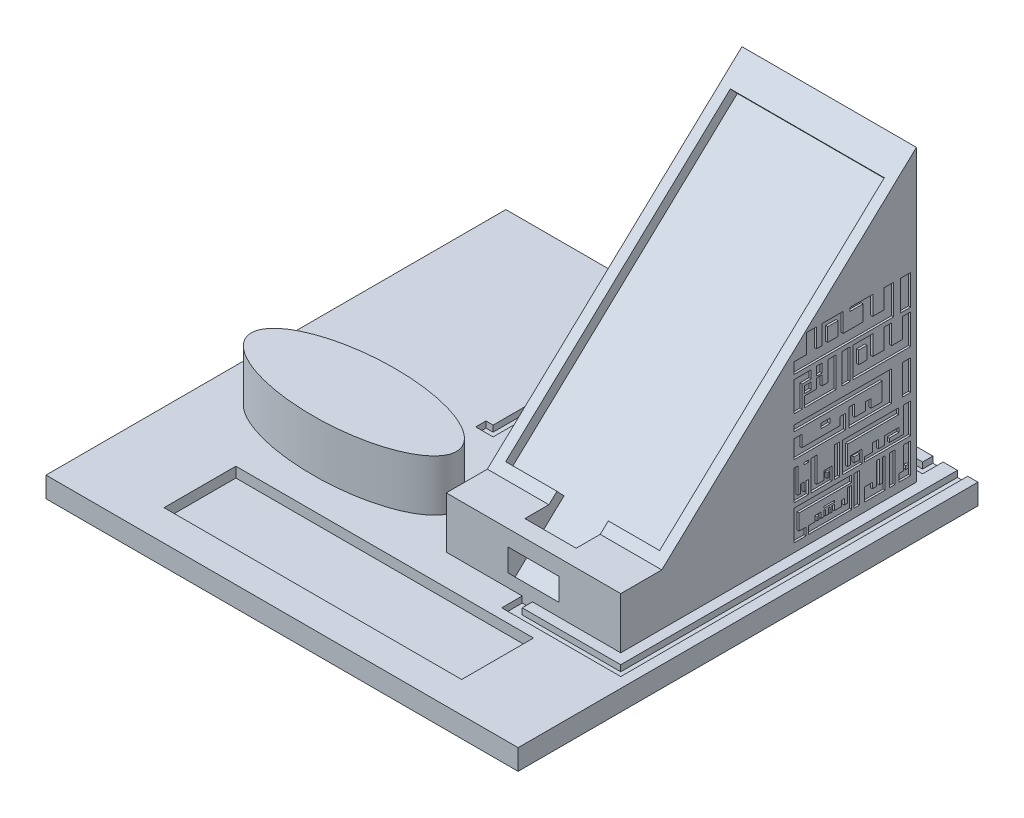
SolidWorks part; units mm, degrees
ref_plane "Front Plane" through (0, 0, 0) normal (0, 0, 1) x (1, 0, 0)
ref_plane "Top Plane" through (0, 0, 0) normal (0, 1, 0) x (1, 0, 0)
ref_plane "Right Plane" through (0, 0, 0) normal (1, 0, 0) x (0, 0, -1)
sketch "Sketch1" plane through (0, 0, 0) normal (0, 1, 0) x (1, 0, 0)
  line L1 (-90.4874, 181.6148) -> (139.5126, 181.6148)
  line L2 (-90.4874, 181.6148) -> (-90.4874, -42.4352)
  line L3 (-90.4874, -42.4352) -> (139.5126, -42.4352)
  line L4 (139.5126, 181.6148) -> (139.5126, -42.4352)
  line L5 (-47.9874, 7.5648) -> (97.0126, 7.5648)
  line L6 (-47.9874, 7.5648) -> (-47.9874, -27.4352)
  line L7 (-47.9874, -27.4352) -> (97.0126, -27.4352)
  line L8 (97.0126, 7.5648) -> (97.0126, -27.4352)
  line L9 (39.5126, 166.6148) -> (124.5126, 166.6148)
  line L10 (39.5126, 166.6148) -> (39.5126, 22.5648)
  line L11 (39.5126, 22.5648) -> (124.5126, 22.5648)
  line L12 (124.5126, 166.6148) -> (124.5126, 22.5648)
  ellipse E0 centre (-25.4874, 42.5648) end of major axis (24.5126, 42.5648) minor radius 20
  dimension "D1" = 15
  dimension "D2" = 15
  dimension "D3" = 145
  dimension "D4" = 35
  dimension "D5" = 85
  dimension "D6" = 144.05
  dimension "D7" = 15
  dimension "D8" = 15
  dimension "D9" = 15
  dimension "D10" = 42.5
  dimension "D11" = 42.5
  dimension "D12" = 15
  dimension "D13" = 15
extrude "Boss-Extrude1" add sketch "Sketch1" against normal blind 10 contours L3 L4 L1 L2
extrude "Boss-Extrude2" add sketch "Sketch1<5>" along normal blind 25 contours E0 region at (-25.4874, 0, -42.5648)
sketch "Sketch1<5>" plane through (0, 0, 0) normal (0, 1, 0) x (1, 0, 0) same geometry as "Sketch1"
extrude "Boss-Extrude3" add sketch "Sketch1<6>" along normal blind 25 contours L12 L9 L10 L11 region at (82.0126, 0, -94.5898)
sketch "Sketch1<6>" plane through (0, 0, 0) normal (0, 1, 0) x (1, 0, 0) same geometry as "Sketch1"
extrude "Cut-Extrude1" cut sketch "Sketch1<8>" against normal blind 5 contours L8 L5 L6 L7 region at (24.5126, 0, 9.9352)
sketch "Sketch1<8>" plane through (0, 0, 0) normal (0, 1, 0) x (1, 0, 0) same geometry as "Sketch1"
sketch "Sketch3" plane through (39.5126, 0, 0) normal (-1, 0, 0) x (0, 0, 1)
  line L0 (-166.6189, 25) -> (-166.6189, 141.2351)
  line L1 (-166.6189, 141.2351) -> (-42.5648, 25)
  line L2 (-166.6148, 25) -> (-22.5648, 25) construction
  line L3 (-42.5648, 25) -> (-166.6189, 25)
  line L4 (-166.6189, 25) -> (-42.5648, 25)
  line M3 (-22.5648, 25) -> (-166.6148, 25)
  dimension "D1" = 170
  dimension "D2" = 20
extrude "Boss-Extrude6" add sketch "Sketch3" against normal up to vertex (85 mm away) contours L1 L0 M3 region at (39.5126, 63.745, -125.2675) up to point (124.5126, 25, -166.6148)
sketch "Sketch5" plane through (0, -7.9248, -7.4253) normal (0, 0.7297, 0.6837) x (1, 0, 0)
  line L0 (39.5126, 218.1542) -> (39.5126, 48.1542) construction
  line L1 (44.5126, 203.5542) -> (119.5126, 203.5542)
  line L2 (44.5126, 203.5542) -> (44.5126, 53.5542)
  line L3 (44.5126, 53.5542) -> (119.5126, 53.5542)
  line L4 (119.5126, 203.5542) -> (119.5126, 53.5542)
  line L5 (124.5126, 218.1542) -> (124.5126, 48.1542) construction
  line L6 (69.5126, 48.1542) -> (94.5126, 48.1542)
  line L7 (124.5126, 48.1542) -> (39.5126, 48.1542) construction
  line L8 (69.5126, 48.1542) -> (69.5126, 15.5805)
  line L9 (69.5126, 15.5805) -> (94.5126, 15.5805)
  line L10 (94.5126, 15.5805) -> (94.5126, 48.1542)
  dimension "D1" = 5
  dimension "D2" = 5
  dimension "D3" = 150
  dimension "D4" = 25
  dimension "D5" = 30
extrude "Cut-Extrude2" cut sketch "Sketch5" against normal blind 5 contours L4 L1 L2 L3 region at (82.0126, 79.9723, -101.2351)
extrude "Cut-Extrude3" cut sketch "Sketch5<3>" along normal blind 8 contours L9 L10 L6 L8
sketch "Sketch5<3>" plane through (0, -7.9248, -7.4253) normal (0, 0.7297, 0.6837) x (1, 0, 0) same geometry as "Sketch5"
sketch "Sketch6" plane through (0, -7.9248, -7.4253) normal (0, 0.7297, 0.6837) x (1, 0, 0)
  line L0 (69.5126, 53.5542) -> (69.5126, 20.7468)
  line L1 (44.5126, 53.5542) -> (119.5126, 53.5542) construction
  line L2 (69.5126, 20.7468) -> (94.5126, 20.7468)
  line L3 (94.5126, 20.7468) -> (94.5126, 53.5542)
  line L4 (94.5126, 53.5542) -> (69.5126, 53.5542)
extrude "Cut-Extrude4" cut sketch "Sketch6" against normal up to surface (5 mm away) up to face at (82.0126, 76.3237, -104.6538)
sketch "Sketch7" plane through (0, 0, 0) normal (0, 1, 0) x (1, 0, 0)
  line L0 (76.5126, 22.5648) -> (76.5126, 12.5648)
  line L1 (39.5126, 22.5648) -> (124.5126, 22.5648) construction
  line L2 (76.5126, 12.5648) -> (134.5126, 12.5648)
  line L3 (134.5126, 12.5648) -> (134.5126, 181.6148)
  line L4 (-90.4874, 181.6148) -> (139.5126, 181.6148) construction
  line L5 (134.5126, 181.6148) -> (129.5126, 181.6148)
  line L6 (129.5126, 181.6148) -> (129.5126, 17.5648)
  line L7 (129.5126, 17.5648) -> (81.5126, 17.5648)
  line L8 (81.5126, 17.5648) -> (81.5126, 22.5648)
  line L9 (39.5126, 22.5648) -> (124.5126, 22.5648) construction
  line L10 (122.5126, 181.6148) -> (122.5126, 171.6148)
  line L11 (122.5126, 171.6148) -> (2.3197, 171.6148)
  line L12 (2.3197, 171.6148) -> (2.3197, 82.5648)
  line L13 (2.3197, 82.5648) -> (-6.1516, 82.5648)
  line L14 (-6.1516, 82.5648) -> (-6.1516, 87.5648)
  line L15 (-6.1516, 87.5648) -> (-2.6803, 87.5648)
  line L16 (-2.6803, 87.5648) -> (-2.6803, 176.6148)
  line L17 (-2.6803, 176.6148) -> (117.5126, 176.6148)
  line L18 (117.5126, 176.6148) -> (117.5126, 181.6148)
  line L19 (117.5126, 181.6148) -> (122.5126, 181.6148)
  line L23 (124.5126, 166.6189) -> (124.5126, 42.5648) construction
  line M5 (139.5126, 181.6148) -> (-90.4874, 181.6148)
  line M7 (124.5126, 22.5648) -> (39.5126, 22.5648)
  dimension "D1" = 5
  dimension "D2" = 5
  dimension "D3" = 5
  dimension "D4" = 5
  dimension "D5" = 5
  dimension "D6" = 5
  dimension "D7" = 5
  dimension "D8" = 5
  dimension "D9" = 7
  dimension "D11" = 5
extrude "Cut-Extrude5" cut sketch "Sketch7" against normal blind 3 contours L7 L8 L0 L2 L3 L6 M7 M5 region at (79.0126, 0, -20.7776)
extrude "Cut-Extrude6" cut sketch "Sketch7<3>" against normal blind 3 contours L16 L17 L18 L19 L10 L11 L12 L13 L14 L15
sketch "Sketch7<3>" plane through (0, 0, 0) normal (0, 1, 0) x (1, 0, 0) same geometry as "Sketch7"
sketch "Sketch14" plane through (0, 0, -166.6189) normal (0, 0, -1) x (-1, 0, 0)
  line L0 (-53.0212, 137.0003) -> (-53.0212, 122.9754)
  line L1 (-53.0212, 122.9754) -> (-103.4158, 122.9754)
  line L2 (-103.4158, 122.9754) -> (-103.4158, 103.7209)
  line L3 (-103.4158, 103.7209) -> (-108.8831, 103.7209)
  line L4 (-108.8831, 103.7209) -> (-108.8831, 136.4733)
  line L5 (-108.8831, 136.4733) -> (-93.432, 136.4733)
  line L6 (-93.432, 136.4733) -> (-93.432, 127.4403)
  line L7 (-93.432, 127.4403) -> (-88.6778, 127.4403)
  line L8 (-88.6778, 127.4403) -> (-88.6778, 136.4733)
  line L9 (-88.6778, 136.4733) -> (-82.9727, 136.4733)
  line L10 (-82.9727, 136.4733) -> (-82.9727, 127.4403)
  line L11 (-82.9727, 127.4403) -> (-78.2185, 127.4403)
  line L12 (-78.2185, 127.4403) -> (-78.2185, 136.4733)
  line L13 (-78.2185, 136.4733) -> (-73.2266, 136.4733)
  line L14 (-73.2266, 136.4733) -> (-73.2266, 127.4403)
  line L15 (-73.2266, 127.4403) -> (-68.2347, 127.4403)
  line L16 (-68.2347, 127.4403) -> (-68.2347, 136.4733)
  line L17 (-68.2347, 136.4733) -> (-63.0051, 136.4733)
  line L18 (-63.0051, 136.4733) -> (-63.0051, 127.9674)
  line L19 (-63.0051, 127.9674) -> (-57.7755, 127.9674)
  line L20 (-57.7755, 127.9674) -> (-57.7755, 137.0003)
  line L21 (-57.7755, 137.0003) -> (-53.0212, 137.0003)
  line L22 (-53.0212, 137.0003) -> (-53.2589, 137.4758)
  line L23 (-103.4158, 132.4838) -> (-103.4158, 127.9674)
  line L24 (-103.4158, 127.9674) -> (-98.1862, 127.9674)
  line L25 (-98.1862, 127.9674) -> (-98.1862, 132.4838)
  line L26 (-98.1862, 132.4838) -> (-103.4158, 132.4838)
  line L27 (-53.0212, 117.0327) -> (-53.0212, 103.7209)
  line L28 (-53.0212, 103.7209) -> (-57.7755, 103.7209)
  line L29 (-57.7755, 103.7209) -> (-57.7755, 117.0327)
  line L30 (-57.7755, 117.0327) -> (-53.0212, 117.0327)
  line L31 (-63.0051, 117.0327) -> (-63.0051, 103.7209)
  line L32 (-63.0051, 103.7209) -> (-98.1862, 103.7209)
  line L33 (-98.1862, 103.7209) -> (-98.1862, 117.0327)
  line L34 (-98.1862, 117.0327) -> (-82.9727, 117.0327)
  line L35 (-82.9727, 117.0327) -> (-82.9727, 108.4751)
  line L36 (-82.9727, 108.4751) -> (-78.2185, 108.4751)
  line L37 (-78.2185, 108.4751) -> (-78.2185, 117.0327)
  line L38 (-78.2185, 117.0327) -> (-73.2266, 117.0327)
  line L39 (-73.2266, 117.0327) -> (-73.2266, 108.4751)
  line L40 (-73.2266, 108.4751) -> (-68.2347, 108.4751)
  line L41 (-68.2347, 108.4751) -> (-68.2347, 117.0327)
  line L42 (-68.2347, 117.0327) -> (-63.0051, 117.0327)
  line L43 (-94.3951, 113.3482) -> (-89.6409, 113.3482)
  line L44 (-89.6409, 113.3482) -> (-89.6409, 108.4751)
  line L45 (-89.6409, 108.4751) -> (-94.3951, 108.4751)
  line L46 (-94.3951, 108.4751) -> (-94.3951, 113.3482)
  line L47 (-53.9844, 98.4913) -> (-53.9844, 93.2617)
  line L48 (-53.9844, 93.2617) -> (-109.8462, 93.2617)
  line L49 (-109.8462, 93.2617) -> (-109.8462, 98.4913)
  line L50 (-109.8462, 98.4913) -> (-53.9844, 98.4913)
  line L51 (-53.9844, 87.5056) -> (-58.7386, 87.5056)
  line L52 (-58.7386, 87.5056) -> (-58.7386, 58.7937)
  line L53 (-58.7386, 58.7937) -> (-63.9682, 58.7937)
  line L54 (-63.9682, 58.7937) -> (-63.9682, 68.5399)
  line L55 (-63.9682, 68.5399) -> (-69.1978, 68.5399)
  line L56 (-69.1978, 68.5399) -> (-69.1978, 58.7937)
  line L57 (-69.1978, 58.7937) -> (-89.6409, 58.7937)
  line L58 (-89.6409, 58.7937) -> (-89.6409, 54.2773)
  line L59 (-89.6409, 54.2773) -> (-53.9844, 54.2773)
  line L60 (-53.9844, 54.2773) -> (-53.9844, 87.5056)
  line L61 (-109.8462, 88.0321) -> (-109.8462, 84.2287)
  line L62 (-109.8462, 84.2287) -> (-69.1978, 84.2287)
  line L63 (-69.1978, 84.2287) -> (-69.1978, 78.5237)
  line L64 (-69.1978, 78.5237) -> (-99.1493, 78.5237)
  line L65 (-99.1493, 78.5237) -> (-99.1493, 58.7937)
  line L66 (-99.1493, 58.7937) -> (-104.3789, 58.7937)
  line L67 (-104.3789, 58.7937) -> (-104.3789, 78.5237)
  line L68 (-104.3789, 78.5237) -> (-109.8462, 78.5237)
  line L69 (-109.8462, 78.5237) -> (-109.8462, 54.2773)
  line L70 (-109.8462, 54.2773) -> (-94.3951, 54.2773)
  line L71 (-94.3951, 54.2773) -> (-94.3951, 73.4129)
  line L72 (-94.3951, 73.4129) -> (-89.522, 73.4129)
  line L73 (-89.522, 73.4129) -> (-89.522, 63.8451)
  line L74 (-89.522, 63.8451) -> (-74.1897, 63.8451)
  line L75 (-74.1897, 63.8451) -> (-74.1897, 73.4129)
  line L76 (-74.1897, 73.4129) -> (-63.9682, 73.4129)
  line L77 (-63.9682, 73.4129) -> (-63.9682, 88.0321)
  line L78 (-63.9682, 88.0321) -> (-109.8462, 88.0321)
  line L79 (-84.1735, 73.4129) -> (-79.4193, 73.4129)
  line L80 (-79.4193, 73.4129) -> (-79.4193, 68.629)
  line L81 (-79.4193, 68.629) -> (-84.1735, 68.629)
  line L82 (-84.1735, 68.629) -> (-84.1735, 73.4129)
  line L83 (-53.9844, 48.2835) -> (-109.8462, 48.2835)
  line L84 (-109.8462, 48.2835) -> (-109.8462, 43.5293)
  line L85 (-109.8462, 43.5293) -> (-53.9844, 43.5293)
  line L86 (-53.9844, 43.5293) -> (-53.9844, 48.2835)
  line L87 (-58.7386, 38.062) -> (-58.7386, 9.2991)
  line L88 (-58.7386, 9.2991) -> (-63.9682, 9.2991)
  line L89 (-63.9682, 9.2991) -> (-63.9682, 19.0452)
  line L90 (-63.9682, 19.0452) -> (-69.1978, 19.0452)
  line L91 (-69.1978, 19.0452) -> (-69.1978, 9.2991)
  line L92 (-69.1978, 9.2991) -> (-109.8462, 9.2991)
  line L93 (-109.8462, 9.2991) -> (-109.8462, 4.7826)
  line L94 (-109.8462, 4.7826) -> (-53.9844, 4.7826)
  line L95 (-53.9844, 4.7826) -> (-53.9844, 38.062)
  line L96 (-53.9844, 38.062) -> (-58.7386, 38.062)
  line L97 (-79.4193, 38.062) -> (-63.9682, 38.062)
  line L98 (-63.9682, 38.062) -> (-63.9682, 23.6805)
  line L99 (-63.9682, 23.6805) -> (-89.522, 23.6805)
  line L100 (-89.522, 23.6805) -> (-89.522, 33.3078)
  line L101 (-89.522, 33.3078) -> (-94.3951, 33.3078)
  line L102 (-94.3951, 33.3078) -> (-94.3951, 23.6805)
  line L103 (-94.3951, 23.6805) -> (-104.3789, 23.6805)
  line L104 (-104.3789, 23.6805) -> (-104.3789, 19.0452)
  line L105 (-104.3789, 19.0452) -> (-76.7451, 19.0452)
  line L106 (-76.7451, 19.0452) -> (-76.7451, 14.1721)
  line L107 (-76.7451, 14.1721) -> (-109.8462, 14.1721)
  line L108 (-109.8462, 14.1721) -> (-109.8462, 38.062)
  line L109 (-109.8462, 38.062) -> (-84.1735, 38.062)
  line L110 (-84.1735, 38.062) -> (-84.1735, 28.4941)
  line L111 (-84.1735, 28.4941) -> (-69.1978, 28.4941)
  line L112 (-69.1978, 28.4941) -> (-69.1978, 33.278)
  line L113 (-69.1978, 33.278) -> (-79.4193, 33.278)
  line L114 (-79.4193, 33.278) -> (-79.4193, 38.062)
  line L115 (-104.3789, 33.8342) -> (-99.387, 33.8342)
  line L116 (-99.387, 33.8342) -> (-99.387, 28.3669)
  line L117 (-99.387, 28.3669) -> (-104.3789, 28.3669)
  line L118 (-104.3789, 28.3669) -> (-104.3789, 33.8342)
  point P121 (0, 0)
  dimension "D5" = 55.8619
  dimension "D8" = 131.6907
extrude "Cut-Extrude7" cut sketch "Sketch14" against normal blind 3 contours L0 L1 L2 L3 L4 L5 L6 L7 L8 L9 L10 L11 L12 L13 L14 L15 L16 L17 L18 L19 L20 L21 | L32 L33 L34 L35 L36 L37 L38 L39 L40 L41 L42 L31 | L27 L28 L29 L30 | L48 L49 L50 L47 | L52 L53 L54 L55 L56 L57 L58 L59 L60 L51 | L77 L78 L61 L62 L63 L64 L65 L66 L67 L68 L69 L70 L71 L72 L73 L74 L75 L76 | L83 L84 L85 L86 | L95 L96 L87 L88 L89 L90 L91 L92 L93 L94 | L98 L99 L100 L101 L102 L103 L104 L105 L106 L107 L108 L109 L110 L111 L112 L113 L114 L97 | L82 L79 L80 L81 | L118 L115 L116 L117 | L25 L26 L23 L24 | L44 L45 L46 L43
sketch "Sketch17" plane through (124.5126, 0, 0) normal (1, 0, 0) x (0, 0, -1)
  line L0 (163.7509, 89.8755) -> (163.7509, 75.2504)
  line L1 (163.7509, 35.6887) -> (163.7509, 21.0637)
  line L2 (163.7509, 35.6887) -> (160.3883, 35.6887)
  line L3 (160.3883, 23.3103) -> (153.4097, 23.3103)
  line L4 (160.3883, 35.6887) -> (160.3883, 23.3103)
  line L5 (163.7509, 75.2504) -> (158.966, 75.2504)
  line L6 (158.966, 75.2504) -> (158.966, 89.8755)
  line L7 (158.966, 89.8755) -> (163.7509, 89.8755)
  line L8 (155.4865, 89.8755) -> (155.4865, 75.2504)
  line L9 (155.4865, 75.2504) -> (155.4865, 89.8755)
  line L10 (150.7016, 89.8755) -> (150.7016, 80.5669)
  line L11 (150.7016, 80.5669) -> (145.3542, 80.5669)
  line L12 (145.3542, 80.5669) -> (145.3542, 89.8755)
  line L13 (145.3542, 89.8755) -> (134.3146, 89.8755)
  line L14 (134.3146, 89.8755) -> (134.3146, 88.2079)
  line L15 (134.3146, 88.2079) -> (140.6177, 88.2079)
  line L16 (140.6177, 88.2079) -> (140.6177, 80.5669)
  line L17 (140.6177, 80.5669) -> (130.8955, 80.5669)
  line L18 (130.8955, 80.5669) -> (130.8955, 89.8755)
  line L19 (130.8955, 89.8755) -> (120.7313, 89.8755)
  line L20 (120.7313, 89.8755) -> (120.7313, 80.5669)
  line L21 (120.7313, 80.5669) -> (117.9693, 80.5669)
  line L22 (117.9693, 80.5669) -> (117.9693, 89.8755)
  line L23 (117.9693, 89.8755) -> (113.1844, 89.8755)
  line L24 (113.1844, 89.8755) -> (113.1844, 80.5669)
  line L25 (113.1844, 80.5669) -> (107.0317, 80.5669)
  line L26 (107.0317, 80.5669) -> (107.0317, 75.2504)
  line L27 (107.0317, 75.2504) -> (155.4865, 75.2504)
  line L28 (136.3964, 27.1688) -> (134.5995, 27.1688)
  line L29 (123.3828, 87.1836) -> (123.3828, 80.5669)
  line L30 (123.3828, 80.5669) -> (128.4393, 80.5669)
  line L31 (128.4393, 80.5669) -> (128.4393, 87.1836)
  line L32 (128.4393, 87.1836) -> (123.3828, 87.1836)
  line L33 (134.5995, 27.1688) -> (134.5995, 23.3103)
  line L34 (150.7016, 89.8755) -> (155.4865, 89.8755)
  line L35 (163.7509, 73.2506) -> (163.7509, 58.6255)
  line L36 (163.7509, 58.6255) -> (159.8999, 58.6255)
  line L37 (159.8999, 73.2506) -> (159.8999, 63.5956)
  line L38 (159.8999, 63.5956) -> (154.5525, 63.5956)
  line L39 (154.5525, 63.5956) -> (154.5525, 73.2506)
  line L40 (154.5525, 73.2506) -> (150.7016, 73.2506)
  line L41 (150.7016, 73.2506) -> (150.7016, 63.5956)
  line L42 (150.7016, 63.5956) -> (145.3542, 63.5956)
  line L43 (145.3542, 63.5956) -> (145.3542, 73.2506)
  line L44 (145.3542, 73.2506) -> (135.7517, 73.2506)
  line L45 (135.7517, 73.2506) -> (135.7517, 58.6255)
  line L46 (135.7517, 58.6255) -> (159.8999, 58.6255)
  line L47 (159.8999, 73.2506) -> (163.7509, 73.2506)
  line L48 (142.5132, 69.8272) -> (138.4798, 69.8272)
  line L49 (138.4798, 69.8272) -> (138.4798, 63.5956)
  line L50 (138.4798, 63.5956) -> (142.5132, 63.5956)
  line L51 (142.5132, 63.5956) -> (142.5132, 69.8272)
  line L52 (133.1522, 14.461) -> (135.1033, 14.461)
  line L53 (134.3146, 73.2506) -> (134.3146, 58.6255)
  line L54 (134.3146, 58.6255) -> (130.4637, 58.6255)
  line L55 (130.4637, 58.6255) -> (130.4637, 73.2506)
  line L56 (130.4637, 73.2506) -> (134.3146, 73.2506)
  line L57 (127.4316, 73.2506) -> (127.4316, 58.6255)
  line L58 (112.0891, 58.6255) -> (127.4316, 58.6255)
  line L59 (151.0136, 27.3684) -> (158.0651, 27.3684)
  line L60 (120.6682, 63.5956) -> (120.6682, 68.2595)
  line L61 (120.6682, 68.2595) -> (117.9506, 68.2595)
  line L62 (117.9506, 68.2595) -> (117.9506, 63.5956)
  line L63 (117.9506, 63.5956) -> (112.0891, 63.5956)
  line L64 (112.0891, 63.5956) -> (112.0891, 58.6255)
  line L65 (158.0651, 25.173) -> (158.0651, 27.3684)
  line L66 (127.4316, 73.2506) -> (123.5807, 73.2506)
  line L67 (123.5807, 73.2506) -> (123.5807, 63.5956)
  line L68 (123.5807, 63.5956) -> (120.6682, 63.5956)
  line L69 (115.3303, 69.2518) -> (115.3303, 73.0449)
  line L70 (115.3303, 73.0449) -> (107.0596, 73.0449)
  line L71 (107.0596, 73.0449) -> (107.0596, 58.6255)
  line L72 (107.0596, 58.6255) -> (110.8904, 58.6255)
  line L73 (110.8904, 58.6255) -> (110.8904, 69.2518)
  line L74 (110.8904, 69.2518) -> (115.3303, 69.2518)
  line L75 (112.0891, 67.9131) -> (112.0891, 64.6631)
  line L76 (112.0891, 64.6631) -> (115.3303, 64.6631)
  line L77 (115.3303, 64.6631) -> (115.3303, 67.9131)
  line L78 (115.3303, 67.9131) -> (112.0891, 67.9131)
  line L79 (117.9506, 69.0586) -> (120.6682, 69.0586)
  line L80 (120.6682, 69.0586) -> (120.6682, 73.2506)
  line L81 (120.6682, 73.2506) -> (117.9506, 73.2506)
  line L82 (117.9506, 73.2506) -> (117.9506, 69.0586)
  line L83 (159.8999, 53.8899) -> (163.7509, 53.8899)
  line L84 (163.7509, 53.8899) -> (163.7509, 39.2648)
  line L85 (163.7509, 39.2648) -> (159.8999, 39.2648)
  line L86 (159.8999, 39.2648) -> (159.8999, 53.8899)
  line L87 (107.0596, 53.8899) -> (154.5525, 53.8899)
  line L88 (154.5525, 53.8899) -> (154.5525, 39.2648)
  line L89 (154.5525, 39.2648) -> (133.768, 39.2648)
  line L90 (133.768, 39.2648) -> (133.768, 48.0938)
  line L91 (133.768, 48.0938) -> (136.4856, 48.0938)
  line L92 (136.4856, 48.0938) -> (136.4856, 42.4185)
  line L93 (136.4856, 42.4185) -> (141.833, 42.4185)
  line L94 (141.833, 42.4185) -> (141.833, 46.3236)
  line L95 (141.833, 46.3236) -> (144.5507, 46.3236)
  line L96 (144.5507, 46.3236) -> (144.5507, 42.2117)
  line L97 (144.5507, 42.2117) -> (149.8981, 42.2117)
  line L98 (149.8981, 42.2117) -> (149.8981, 51.0477)
  line L99 (149.8981, 51.0477) -> (107.0596, 51.0477)
  line L100 (107.0596, 51.0477) -> (107.0596, 53.8899)
  line L101 (129.3931, 46.3236) -> (132.1108, 46.3236)
  line L102 (132.1108, 46.3236) -> (132.1108, 39.2648)
  line L103 (132.1108, 39.2648) -> (107.0596, 39.2648)
  line L104 (107.0596, 39.2648) -> (107.0596, 48.0938)
  line L105 (107.0596, 48.0938) -> (110.8171, 48.0938)
  line L106 (110.8171, 48.0938) -> (110.8171, 42.4185)
  line L107 (110.8171, 42.4185) -> (129.3931, 42.4185)
  line L108 (129.3931, 42.4185) -> (129.3931, 46.3236)
  line L109 (124.4099, 48.0938) -> (120.1218, 48.0938)
  line L110 (120.1218, 48.0938) -> (120.1218, 45.7827)
  line L111 (120.1218, 45.7827) -> (124.4099, 45.7827)
  line L112 (124.4099, 45.7827) -> (124.4099, 48.0938)
  line L113 (145.1752, 27.3019) -> (148.0644, 27.3019)
  line L114 (151.0136, 27.3684) -> (151.0136, 23.3103)
  line L115 (151.0136, 23.3103) -> (148.0644, 23.3103)
  line L116 (148.0644, 23.3103) -> (148.0644, 27.3019)
  line L117 (135.1033, 14.461) -> (135.1033, 10.6261)
  line L118 (145.1752, 27.3019) -> (145.1752, 23.3103)
  line L119 (145.1752, 23.3103) -> (141.3414, 23.3103)
  line L120 (141.3414, 23.3103) -> (141.3414, 21.0637)
  line L121 (141.3414, 21.0637) -> (163.7509, 21.0637)
  line L122 (140.2127, 27.1688) -> (140.2127, 21.0637)
  line L123 (140.2127, 21.0637) -> (130.4871, 21.0637)
  line L124 (134.5995, 23.3103) -> (133.1557, 23.3103)
  line L125 (157.9089, 35.6887) -> (130.4871, 35.6887)
  line L126 (130.4871, 35.6887) -> (130.4871, 21.0637)
  line L127 (121.503, 27.3684) -> (125.537, 27.3684)
  line L128 (157.9089, 35.6887) -> (157.9089, 32.8236)
  line L129 (136.3964, 27.1688) -> (140.2127, 27.1688)
  line L130 (136.2965, 25.8383) -> (138.9079, 25.8383)
  line L131 (138.9079, 25.8383) -> (138.9079, 23.3103)
  line L132 (138.9079, 23.3103) -> (136.2965, 23.3103)
  line L133 (123.0111, 23.3103) -> (123.0111, 25.6387)
  line L134 (136.2965, 25.8383) -> (136.2965, 23.3103)
  line L135 (157.9089, 32.8236) -> (133.1557, 32.8236)
  line L136 (133.1557, 32.8236) -> (133.1557, 23.3103)
  line L137 (129.2293, 35.6887) -> (129.2293, 21.0637)
  line L138 (129.2293, 21.0637) -> (126.6211, 21.0637)
  line L139 (126.6211, 21.0637) -> (126.6211, 35.6887)
  line L140 (126.6211, 35.6887) -> (129.2293, 35.6887)
  line L141 (123.0111, 25.6387) -> (124.0986, 25.6387)
  line L142 (133.1522, 14.461) -> (133.1522, 10.6261)
  line L143 (121.503, 23.3103) -> (121.503, 27.3684)
  line L145 (121.503, 23.3103) -> (118.1167, 23.3103)
  line L146 (118.1167, 23.3103) -> (118.1167, 35.6887)
  line L147 (118.1167, 35.6887) -> (115.3464, 35.6887)
  line L148 (115.3464, 35.6887) -> (115.3464, 21.0637)
  line L149 (115.3464, 21.0637) -> (125.537, 21.0637)
  line L151 (124.0986, 25.6387) -> (124.0986, 23.3103)
  line L153 (153.4097, 25.173) -> (158.0651, 25.173)
  line L154 (124.0986, 23.3103) -> (123.0111, 23.3103)
  line L155 (125.537, 21.1814) -> (125.537, 27.3684)
  line L156 (125.537, 21.1814) -> (125.537, 21.0637)
  line L157 (113.9228, 27.4349) -> (113.9228, 21.0637)
  line L158 (113.9228, 21.0637) -> (107.0596, 21.0637)
  line L159 (107.0596, 21.0637) -> (107.0596, 35.6887)
  line L160 (107.0596, 35.6887) -> (108.87, 35.6887)
  line L161 (108.87, 35.6887) -> (108.87, 23.3103)
  line L162 (108.87, 23.3103) -> (110.1332, 23.3103)
  line L163 (110.1332, 23.3103) -> (110.1332, 27.4349)
  line L164 (110.1332, 27.4349) -> (111.8174, 27.4349)
  line L165 (111.8174, 27.4349) -> (111.8174, 23.3103)
  line L166 (111.8174, 23.3103) -> (112.8701, 23.3103)
  line L167 (112.8701, 23.3103) -> (112.8701, 27.4349)
  line L168 (112.8701, 27.4349) -> (113.9228, 27.4349)
  line L169 (111.8174, 35.6887) -> (113.9228, 35.6887)
  line L170 (113.9228, 35.6887) -> (113.9228, 34.6596)
  line L171 (113.9228, 34.6596) -> (111.8174, 34.6596)
  line L172 (111.8174, 34.6596) -> (111.8174, 35.6887)
  line L173 (109.5016, 35.6887) -> (110.5967, 35.6887)
  line L174 (110.5967, 35.6887) -> (110.5967, 34.6289)
  line L175 (110.5967, 34.6289) -> (109.5016, 34.6289)
  line L176 (109.5016, 34.6289) -> (109.5016, 35.6887)
  line L177 (160.3848, 18.83) -> (163.7475, 18.83)
  line L178 (163.7475, 18.83) -> (163.7475, 4.2049)
  line L179 (163.7475, 4.2049) -> (158.2289, 4.2049)
  line L180 (158.2289, 4.2049) -> (158.2289, 7.9105)
  line L181 (160.3848, 18.83) -> (160.3848, 7.9105)
  line L182 (160.3848, 7.9105) -> (158.2289, 7.9105)
  line L183 (161.4025, 9.5409) -> (161.4025, 7.9105)
  line L184 (161.4025, 7.9105) -> (162.8186, 7.9105)
  line L185 (162.8186, 7.9105) -> (162.8186, 9.5409)
  line L186 (162.8186, 9.5409) -> (161.4025, 9.5409)
  line L187 (156.0847, 18.83) -> (156.0847, 4.2049)
  line L188 (156.0847, 4.2049) -> (153.4097, 4.2049)
  line L189 (153.4097, 4.2049) -> (153.4097, 18.83)
  line L190 (153.4097, 18.83) -> (156.0847, 18.83)
  line L191 (151.3991, 18.83) -> (151.3991, 4.2049)
  line L192 (151.3991, 4.2049) -> (141.338, 4.2049)
  line L193 (141.338, 4.2049) -> (141.338, 10.6261)
  line L194 (141.338, 10.6261) -> (145.1718, 10.6261)
  line L195 (145.1718, 10.6261) -> (145.1718, 7.9105)
  line L196 (145.1718, 7.9105) -> (147.1598, 7.9105)
  line L197 (147.1598, 7.9105) -> (147.1598, 18.83)
  line L198 (147.1598, 18.83) -> (148.515, 18.83)
  line L199 (148.515, 18.83) -> (148.515, 7.9105)
  line L200 (148.515, 7.9105) -> (150.0046, 7.9105)
  line L201 (150.0046, 7.9105) -> (150.0046, 18.83)
  line L202 (150.0046, 18.83) -> (151.3991, 18.83)
  line L203 (142.6973, 9.5409) -> (143.9022, 9.5409)
  line L204 (143.9022, 9.5409) -> (143.9022, 7.9105)
  line L205 (143.9022, 7.9105) -> (142.6973, 7.9105)
  line L206 (142.6973, 7.9105) -> (142.6973, 9.5409)
  line L207 (138.9079, 18.83) -> (138.9079, 4.2049)
  line L208 (138.9079, 4.2049) -> (136.2965, 4.2049)
  line L209 (136.2965, 4.2049) -> (136.2965, 18.83)
  line L210 (136.2965, 18.83) -> (138.9079, 18.83)
  line L212 (135.1033, 10.6261) -> (135.1033, 4.2049)
  line L213 (135.1033, 4.2049) -> (113.9194, 4.2049)
  line L214 (113.9194, 4.2049) -> (113.9194, 7.9105)
  line L215 (113.9194, 7.9105) -> (117.3022, 7.9105)
  line L216 (117.3022, 7.9105) -> (117.3022, 10.6261)
  line L217 (117.3022, 10.6261) -> (120.092, 10.6261)
  line L218 (120.092, 10.6261) -> (120.092, 7.9105)
  line L219 (120.092, 7.9105) -> (121.4996, 7.9105)
  line L220 (121.4996, 7.9105) -> (121.4996, 10.6261)
  line L221 (121.4996, 10.6261) -> (122.372, 10.6261)
  line L222 (122.372, 10.6261) -> (122.372, 7.9105)
  line L223 (122.372, 7.9105) -> (123.6677, 7.9105)
  line L224 (123.6677, 7.9105) -> (123.6677, 10.6261)
  line L225 (123.6677, 10.6261) -> (124.5113, 10.6261)
  line L226 (124.5113, 10.6261) -> (124.5113, 7.9105)
  line L227 (124.5113, 7.9105) -> (125.5335, 7.9105)
  line L228 (125.5335, 7.9105) -> (125.5335, 10.6261)
  line L229 (125.5335, 10.6261) -> (126.6176, 10.6261)
  line L230 (126.6176, 10.6261) -> (126.6176, 7.9105)
  line L231 (126.6176, 7.9105) -> (130.0692, 7.9105)
  line L232 (130.0692, 7.9105) -> (130.0692, 10.6261)
  line L233 (130.0692, 10.6261) -> (131.4623, 10.6261)
  line L234 (131.4623, 10.6261) -> (131.4623, 7.9105)
  line L235 (131.4623, 7.9105) -> (133.1522, 7.9105)
  line L236 (133.1522, 7.9105) -> (133.1522, 10.6261)
  line L237 (118.1132, 9.5409) -> (119.266, 9.5409)
  line L238 (119.266, 9.5409) -> (119.266, 7.9105)
  line L239 (119.266, 7.9105) -> (118.1132, 7.9105)
  line L240 (118.1132, 7.9105) -> (118.1132, 9.5409)
  line L241 (112.8667, 4.2049) -> (107.0596, 4.2049)
  line L242 (107.0596, 4.2049) -> (107.0596, 18.83)
  line L243 (107.0596, 18.83) -> (135.1033, 18.83)
  line L244 (135.1033, 18.83) -> (135.1033, 15.5804)
  line L245 (135.1033, 15.5804) -> (109.4981, 15.5804)
  line L246 (109.4981, 15.5804) -> (109.4981, 7.9105)
  line L247 (109.4981, 7.9105) -> (112.8667, 7.9105)
  line L248 (112.8667, 7.9105) -> (112.8667, 4.2049)
  line L249 (121.4996, 11.5215) -> (126.6176, 11.5215)
  line L250 (126.6176, 11.5215) -> (126.6176, 12.3005)
  line L251 (126.6176, 12.3005) -> (121.4996, 12.3005)
  line L252 (121.4996, 11.5215) -> (121.4996, 12.3005)
  line L253 (127.8202, 11.4936) -> (127.8202, 12.3005)
  line L254 (127.8202, 12.3005) -> (128.7478, 12.3005)
  line L255 (128.7478, 12.3005) -> (128.7478, 11.4936)
  line L256 (128.7478, 11.4936) -> (127.8202, 11.4936)
  line L257 (153.4097, 25.173) -> (153.4097, 23.3103)
  dimension "D1" = 14.6251
extrude "Cut-Extrude9" cut sketch "Sketch17" against normal blind 1 contours L7 L6 L5 L0 | L34 L10 L11 L12 L13 L14 L15 L16 L17 L18 L19 L20 L21 L22 L23 L24 L25 L26 L27 L8 L32 L31 L30 L29 | L47 L37 L38 L39 L40 L41 L42 L43 L44 L45 L46 L36 L35 L51 L50 L49 L48 | L56 L55 L54 L53 | L67 L68 L60 L61 L62 L63 L64 L58 L57 L66 | L73 L74 L69 L70 L71 L72 | L86 L85 L84 L83 | L100 L99 L98 L97 L96 L95 L94 L93 L92 L91 L90 L89 L88 L87 | L111 L112 L109 L110 | L108 L107 L106 L105 L104 L103 L102 L101 | L257 L153 L65 L59 L114 L115 L116 L113 L118 L119 L120 L121 L1 L2 L4 L3 | L136 L135 L128 L125 L126 L123 L122 L129 L28 L33 L124 L134 L130 L131 L132 | L156 L155 L127 L143 L145 L146 L147 L148 L149 L151 L154 L133 L141 | L168 L167 L166 L165 L164 L163 L162 L161 L160 L159 L158 L157 | L181 L182 L180 L179 L178 L177 L186 L185 L184 L183 | L190 L189 L188 L187 | L210 L209 L208 L207 | L248 L247 L246 L245 L244 L243 L242 L241 | L236 L235 L234 L233 L232 L231 L230 L229 L228 L227 L226 L225 L224 L223 L222 L221 L220 L219 L218 L217 L216 L215 L214 L213 L212 L117 L52 L142 L239 L240 L237 L238 | L80 L81 L82 L79 | L78 L75 L76 L77 | L139 L140 L137 L138 | L171 L172 L169 L170 | L191 L192 L193 L194 L195 L196 L197 L198 L199 L200 L201 L202 | L251 L252 L249 L250 region at (124.5126, 82.5629, -161.3584) region at (124.5126, 25.5304, -155.4415) region at (124.5126, 82.5629, -154.9803) region at (124.5126, 26.8581, -138.3045) region at (124.5126, 65.938, -163.435) region at (124.5126, 7.1781, -125.5356) region at (124.5126, 65.938, -132.3891) region at (124.5126, 65.938, -127.2196) region at (124.5126, 67.0766, -109.9412) region at (124.5126, 46.5773, -161.8254) region at (124.5126, 53.3929, -130.806) region at (124.5126, 42.0278, -118.6069) region at (124.5126, 46.9383, -122.2659) region at (124.5126, 27.1902, -123.52) region at (124.5126, 24.2493, -113.7612) region at (124.5126, 10.8399, -161.6625) region at (124.5126, 11.5174, -154.7472) region at (124.5126, 11.5174, -137.6022) region at (124.5126, 4.5212, -109.9631)
sketch "Sketch18" plane through (0, -10, 0) normal (0, -1, 0) x (1, 0, 0)
  line L0 (-90.4874, 42.4352) -> (139.5126, 42.4352) construction
  line L1 (-80.4874, 32.4352) -> (129.5126, 32.4352)
  line L2 (-80.4874, 32.4352) -> (-80.4874, -13.133)
  line L3 (-80.4874, -13.133) -> (129.5126, -13.133)
  line L4 (129.5126, 32.4352) -> (129.5126, -13.133)
  line L5 (-80.4874, -23.133) -> (-23.2192, -23.133)
  line L6 (-80.4874, -23.133) -> (-80.4874, -116.0466)
  line L7 (-80.4874, -116.0466) -> (-23.2192, -116.0466)
  line L8 (-23.2192, -23.133) -> (-23.2192, -116.0466)
  line L9 (72.2444, -23.133) -> (129.5126, -23.133)
  line L10 (72.2444, -23.133) -> (72.2444, -116.0466)
  line L11 (72.2444, -116.0466) -> (129.5126, -116.0466)
  line L12 (129.5126, -23.133) -> (129.5126, -116.0466)
  line L13 (-80.4874, -126.0466) -> (129.5126, -126.0466)
  line L14 (-80.4874, -126.0466) -> (-80.4874, -171.6148)
  line L15 (-80.4874, -171.6148) -> (129.5126, -171.6148)
  line L16 (129.5126, -126.0466) -> (129.5126, -171.6148)
  line L17 (-90.4874, -181.6148) -> (139.5126, -181.6148) construction
  line L18 (139.5126, -181.6148) -> (139.5126, 42.4352) construction
  line L19 (-90.4874, -181.6148) -> (-90.4874, 42.4352) construction
  dimension "D1" = 10
  dimension "D2" = 10
  dimension "D3" = 10
  dimension "D4" = 10
  dimension "D5" = 10
  dimension "D6" = 10
extrude "Cut-Extrude10" cut sketch "Sketch18" against normal blind 3
